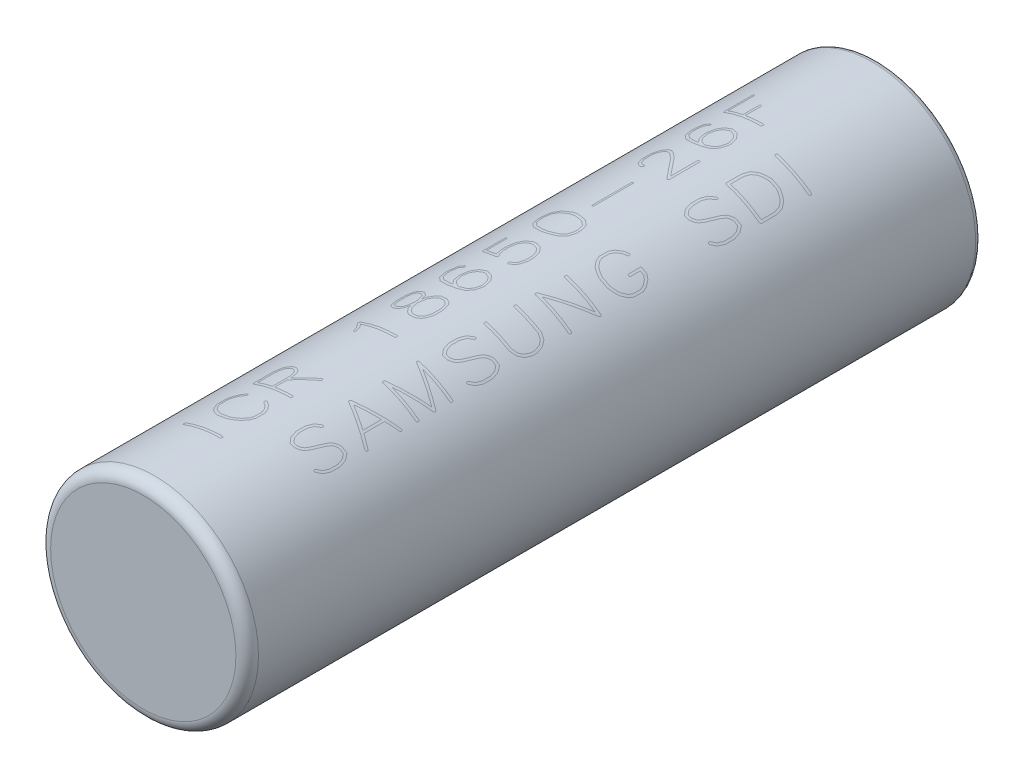
SolidWorks part; units mm, degrees
ref_plane "Alzado" through (0, 0, 0) normal (0, 0, 1) x (1, 0, 0)
ref_plane "Planta" through (0, 0, 0) normal (0, 1, 0) x (1, 0, 0)
ref_plane "Vista lateral" through (0, 0, 0) normal (1, 0, 0) x (0, 0, -1)
sketch "Croquis1" plane through (0, 0, 0) normal (0, 0, 1) x (1, 0, 0)
  circle A0 centre (0, 0) radius 9.2
  dimension "D1" = 18.4
extrude "Saliente-Extruir1" add sketch "Croquis1" along normal blind 65
fillet "Redondeo1" radius 1 1 edges at (9.2, 0, 65)
fillet "Redondeo2" radius 0.5 1 edges at (9.2, 0, 0)
ref_plane "Plano1" through (0, 9.2, 0) normal (0, 1, 0) x (1, 0, 0)
sketch "Croquis2" plane through (0, 9.2, 0) normal (0, 1, 0) x (1, 0, 0)
  line L0 (0, 0) -> (0, -65) construction
  line L1 (-8.2, -65) -> (8.2, -65) construction
  text T0 "ICR 18650-26F\r\nSAMSUNG SDI" font "SWSimp" height 3.5
wrap "Envolver1" sketch "Croquis2" wrap type scribe source sketch "Croquis2" face at (9.2, 0, 0.5)
ref_axis "Eje1" through (0, 0, 64) along (0, 0, -1)
